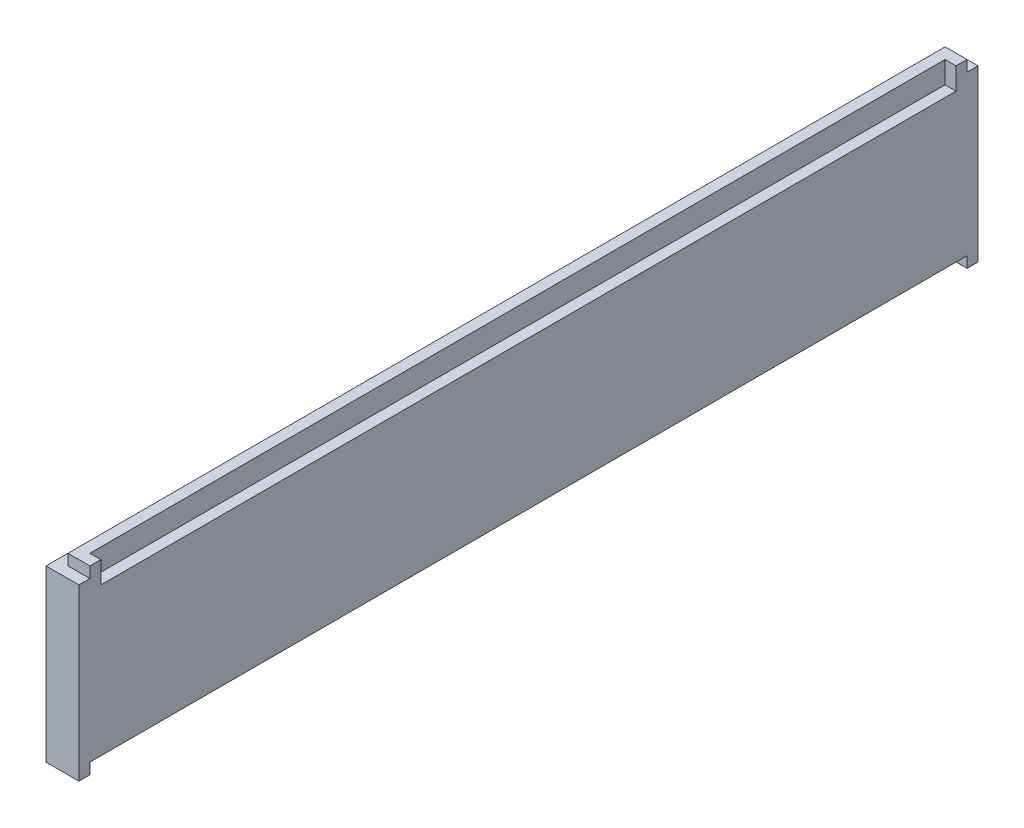
SolidWorks part; units mm, degrees
material "Сосна"
ref_plane "Спереди" through (0, 0, 0) normal (0, 0, 1) x (1, 0, 0)
ref_plane "Сверху" through (0, 0, 0) normal (0, 1, 0) x (1, 0, 0)
ref_plane "Справа" through (0, 0, 0) normal (1, 0, 0) x (0, 0, -1)
sketch "Эскиз1" plane through (0, 0, 0) normal (0, 0, 1) x (1, 0, 0)
  line L0 (0, 0) -> (0, 155)
  line L1 (0, 155) -> (10, 155)
  line L2 (10, 155) -> (10, 165)
  line L3 (10, 165) -> (20, 165)
  line L4 (20, 165) -> (20, 145)
  line L5 (20, 145) -> (30, 145)
  line L6 (30, 145) -> (30, 10)
  line L7 (30, 10) -> (10, 10)
  line L8 (10, 10) -> (10, 0)
  line L9 (10, 0) -> (0, 0)
  dimension "D1" = 10
  dimension "D2" = 10
  dimension "D3" = 10
  dimension "D4" = 10
  dimension "D5" = 20
  dimension "D6" = 10
  dimension "D7" = 10
  dimension "D8" = 155
extrude "Бобышка-Вытянуть1" add sketch "Эскиз1" along normal blind 820
sketch "Эскиз2" plane through (10, 0, 0) normal (1, 0, 0) x (0, 0, -1)
  line L0 (-820, 10) -> (0, 10) construction
  line L1 (-820, 0) -> (-810, 0)
  line L2 (-820, 0) -> (-820, 10)
  line L3 (-820, 10) -> (-810, 10)
  line L4 (-810, 0) -> (-810, 10)
  line L5 (-410, 0) -> (-410, 171.2653) construction
  line L6 (-820, 0) -> (0, 0) construction
  line L7 (-10, 0) -> (-10, 10)
  line L8 (0, 10) -> (-10, 10)
  line L9 (0, 0) -> (0, 10)
  line L10 (0, 0) -> (-10, 0)
  dimension "D1" = 10
extrude "Бобышка-Вытянуть2" add sketch "Эскиз2" along normal up to surface (20 mm away) up to face at (30, 77.5, 410)
sketch "Эскиз4" plane through (20, 0, 0) normal (1, 0, 0) x (0, 0, -1)
  line L0 (-820, 145) -> (0, 145) construction
  line L1 (-820, 165) -> (-800, 165)
  line L2 (-820, 165) -> (-820, 145)
  line L3 (-820, 145) -> (-800, 145)
  line L4 (-800, 165) -> (-800, 145)
  line L5 (-410, 165) -> (-410, 0) construction
  line L6 (-820, 165) -> (0, 165) construction
  line L7 (-20, 165) -> (-20, 145)
  line L8 (0, 145) -> (-20, 145)
  line L9 (0, 165) -> (0, 145)
  line L10 (0, 165) -> (-20, 165)
  dimension "D1" = 20
extrude "Бобышка-Вытянуть3" add sketch "Эскиз4" along normal up to surface (10 mm away) up to face at (30, 38.75, 410)
sketch "Эскиз5" plane through (30, 0, 0) normal (1, 0, 0) x (0, 0, -1)
  line L0 (-410, 145) -> (-410, 0) construction
  line L1 (-820, 165) -> (-810, 165)
  line L2 (-820, 165) -> (-820, 155)
  line L3 (-820, 155) -> (-810, 155)
  line L4 (-810, 165) -> (-810, 155)
  line L5 (-800, 145) -> (-20, 145) construction
  line L6 (-10, 165) -> (-10, 155)
  line L7 (0, 155) -> (-10, 155)
  line L8 (0, 165) -> (0, 155)
  line L9 (0, 165) -> (-10, 165)
  dimension "D1" = 10
  dimension "D2" = 10
extrude "Вырез-Вытянуть2" cut sketch "Эскиз5" against normal through all
